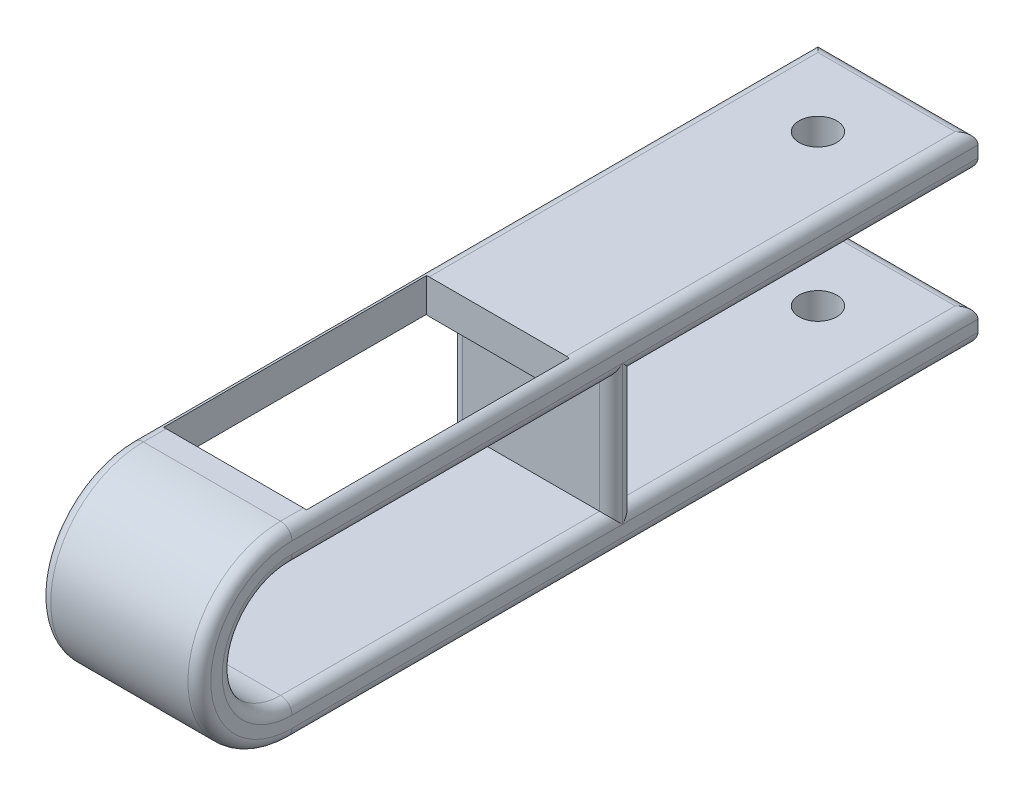
SolidWorks part; units mm, degrees
material "PLA"
ref_plane "Front Plane" through (0, 0, 0) normal (1, 0, 0) x (0, 1, 0)
ref_plane "Top Plane" through (0, 0, 0) normal (0, 0, 1) x (0, 1, 0)
ref_plane "Right Plane" through (0, 0, 0) normal (0, 1, 0) x (-1, 0, 0)
sketch "Sketch2" plane through (0, 0, 0) normal (1, 0, 0) x (0, 1, 0)
  line L0 (0, 0) -> (0, 67.6733) construction
  line L1 (8.1, 0) -> (5.1, 0)
  line L3 (-8.1, 60) -> (-8.1, 0)
  line L4 (-8.1, 0) -> (-5.1, 0)
  line L5 (-5.1, 60) -> (-5.1, 32.1)
  line L6 (5.1, 60) -> (5.1, 32.1)
  line L8 (8.1, 60) -> (8.1, 0)
  line L9 (0, 0) -> (-21.6048, 0) construction
  line L10 (-5.1, 30.1) -> (-5.1, 0)
  line L11 (-5.1, 32.1) -> (5.1, 32.1)
  line L13 (-5.1, 30.1) -> (5.1, 30.1)
  line L15 (5.1, 30.1) -> (5.1, 0)
  arc A0 (5.1, 60) -> (-5.1, 60) centre (0, 60) ccw
  arc A1 (8.1, 60) -> (-8.1, 60) centre (0, 60) ccw
  point P16 (0, 65.1)
  dimension "D4" = 2
  dimension "D1" = 3
  dimension "D2" = 60
  dimension "D3" = 5.1
  dimension "D5" = 33
extrude "Boss-Extrude1" add sketch "Sketch2" along normal blind 14
sketch "Sketch3" plane through (0, -8.1, 0) normal (0, -1, 0) x (1, 0, 0)
  line L0 (7, 0) -> (7, 60) construction
  line L1 (14, 0) -> (0, 0) construction
  line L2 (14, 60) -> (0, 60) construction
  line L3 (0, 60) -> (0, 0) construction
  line L4 (14, 60) -> (14, 0) construction
  circle A0 centre (7, 7) radius 1.65
  dimension "D1" = 3.3
  dimension "D2" = 7
extrude "Cut-Extrude1" cut sketch "Sketch3" against normal blind 40
sketch "Sketch4" plane through (0, -8.1, 0) normal (0, -1, 0) x (1, 0, 0)
  line L0 (7, 60) -> (7, 40.4256) construction
  line L1 (14, 60) -> (0, 60) construction
  line L2 (9.35, 38) -> (10.6, 53)
  line L3 (3.4, 53) -> (4.65, 38)
  circle A0 centre (7, 53) radius 3.6
  circle A1 centre (7, 38) radius 2.35
  dimension "D1" = 7.2
  dimension "D2" = 4.7
  dimension "D3" = 7
  dimension "D4" = 15
extrude "Cut-Extrude2" cut sketch "Sketch4" against normal blind 1.5 contours A1 L2 A0 L3 | L0 A0 L3 | A0 L0 L2 | A1 region at (8.5274, -8.1, 53.0001) region at (5.4726, -8.1, 53.0001) region at (9.4291, -8.1, 50.1292) region at (7, -8.1, 38)
sketch "Sketch6" plane through (0, -6.6, 0) normal (0, -1, 0) x (1, 0, 0)
  line L0 (7, 35.65) -> (7, 56.6) construction
  circle A0 centre (7, 38) radius 0.15
  arc A1 (4.65, 38) -> (9.35, 38) centre (7, 38) ccw construction
  arc A2 (10.6, 53) -> (3.4, 53) centre (7, 53) ccw construction
  arc A3 (4.65, 38) -> (9.35, 38) centre (7, 38) ccw construction
  dimension "D1" = 0.3
extrude "Cut-Extrude3" cut sketch "Sketch6" against normal blind 0.5
ref_plane "Plane1" through (10.6, -8.1, 53) normal (0, 0, 1) x (1, 0, 0)
sketch "Sketch8" plane through (0, -6.6, 0) normal (0, -1, 0) x (1, 0, 0)
  circle A0 centre (7, 53) radius 0.15
  arc A1 (10.6, 53) -> (3.4, 53) centre (7, 53) ccw construction
  dimension "D1" = 0.3
extrude "Cut-Extrude4" cut sketch "Sketch8" against normal blind 0.5
sketch "Sketch9" plane through (0, 8.1, 0) normal (0, 1, 0) x (-1, 0, 0)
  line L1 (-14, 60) -> (0, 60) construction
  line L2 (-0.75, 35) -> (-13.25, 35)
  line L3 (-0.75, 35) -> (-0.75, 58)
  line L4 (-0.75, 58) -> (-13.25, 58)
  line L5 (-13.25, 35) -> (-13.25, 58)
  line L6 (-0.75, 35) -> (-13.25, 58) construction
  line L7 (-0.75, 58) -> (-13.25, 35) construction
  line L8 (-14, 0) -> (-14, 60) construction
  point P6 (-7, 46.5)
  dimension "D1" = 2
  dimension "D2" = 12.5
  dimension "23" = 23
  dimension "D3" = 0.75
extrude "Cut-Extrude5" cut sketch "Sketch9" against normal up to next
fillet "Fillet1" radius 1 24 edges at (0, 8.1, 30) (0, -8.1, 30) (0, -5.1, 46.05) (0, 0, 65.1) (14, 0, 32.1) (0, 0, 32.1) (0, -5.1, 15.05) (0, 0, 30.1) (0, 5.1, 15.05) (0, 0, 68.1) (0, 5.1, 46.05) (14, 0, 65.1) (14, 0, 68.1) (14, 8.1, 30) (14, -5.1, 46.05) (14, -5.1, 15.05) (14, 0, 30.1) (14, 5.1, 15.05) (14, 5.1, 46.05) (14, -8.1, 30) (7, -8.1, 0) (7, -5.1, 0) (7, 5.1, 0) (7, 8.1, 0)
